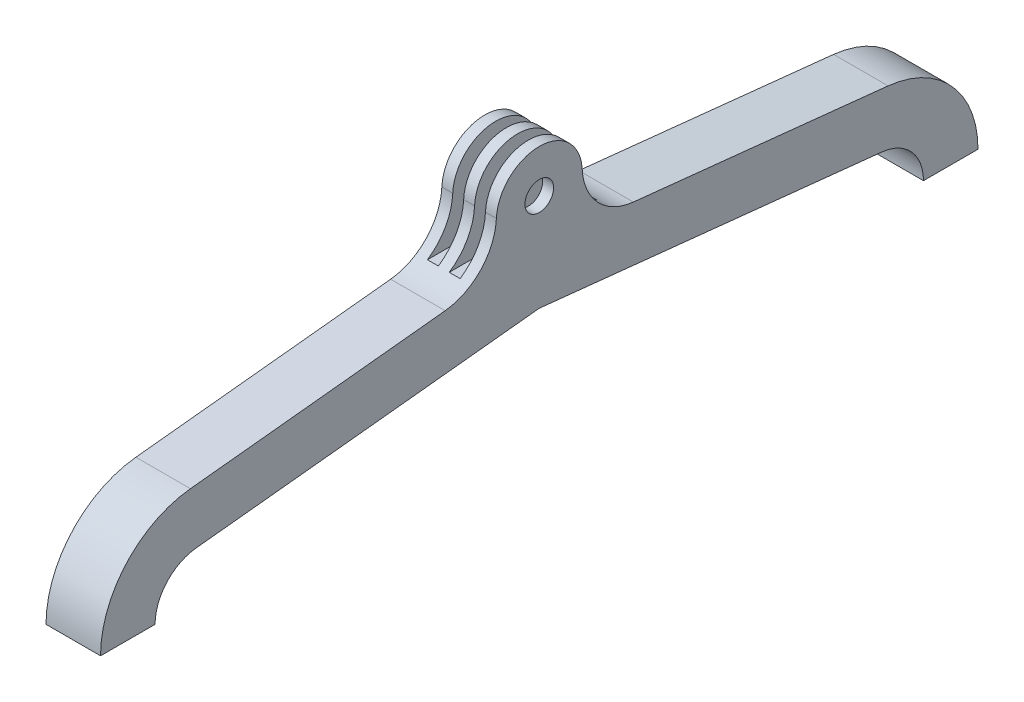
SolidWorks part; units mm, degrees
ref_plane "Front Plane" through (0, 0, 0) normal (0, 0, 1) x (1, 0, 0)
ref_plane "Top Plane" through (0, 0, 0) normal (0, 1, 0) x (1, 0, 0)
ref_plane "Right Plane" through (0, 0, 0) normal (1, 0, 0) x (0, 0, -1)
sketch "Sketch1" plane through (0, 0, 0) normal (1, 0, 0) x (0, 0, -1)
  line L0 (0, 0) -> (575, 0) construction
  line L1 (45.7424, 50.8) -> (287.5, 76.2)
  line L2 (575, 0) -> (575, -43.6699) construction
  line L3 (0, 0) -> (0, -49.9019) construction
  line L4 (287.5, 76.2) -> (529.2576, 50.8)
  arc A0 (0, 0) -> (45.7424, 50.8) centre (51.0796, 0) cw
  arc A1 (529.2576, 50.8) -> (575, 0) centre (523.9204, 0) cw
  dimension "D1" = 575
  dimension "D2" = 50.8
  dimension "D3" = 76.2
sketch "Sketch2" plane through (0, 0, 0) normal (0, 1, 0) x (1, 0, 0)
  line L0 (-19.05, -19.05) -> (19.05, -19.05)
  line L1 (-19.05, -19.05) -> (-19.05, 19.05)
  line L2 (19.05, -19.05) -> (19.05, 19.05)
  line L3 (-19.05, 19.05) -> (19.05, 19.05)
  line L4 (-19.05, -19.05) -> (19.05, 19.05) construction
  line L5 (19.05, -19.05) -> (-19.05, 19.05) construction
  point P1 (0, 0)
  dimension "D1" = 38.1
sweep "Sweep1" add profiles "Sketch2" path "Sketch1"
ref_point "Point1"
ref_point "Point2"
ref_axis "Axis1" through (0, 0, -575) along (0, -1, 0)
ref_axis "Axis2" through (0, 0, 0) along (0, -1, 0)
sketch "Sketch3" plane through (19.05, 0, 0) normal (1, 0, 0) x (0, 0, -1)
  line L6 (-19.05, 0) -> (19.05, 0)
  line L7 (47.7329, 31.8543) -> (287.5, 57.0451)
  line L8 (287.5, 57.0451) -> (527.2671, 31.8543)
  line L9 (555.95, 0) -> (594.05, 0)
  line L10 (531.2482, 69.7457) -> (287.5, 95.3549)
  line L11 (287.5, 95.3549) -> (43.7518, 69.7457)
  line L12 (-19.05, 0) -> (19.05, 0)
  line L13 (47.7329, 31.8543) -> (287.5, 57.0451)
  line L14 (287.5, 57.0451) -> (527.2671, 31.8543)
  line L15 (555.95, 0) -> (594.05, 0)
  line L16 (531.2482, 69.7457) -> (287.5, 95.3549)
  line L17 (287.5, 95.3549) -> (43.7518, 69.7457)
  circle A0 centre (287.5, 125) radius 10
  circle A1 centre (287.5, 125) radius 30
  arc A6 (43.7518, 69.7457) -> (-19.05, 0) centre (51.0796, 0) ccw
  arc A7 (47.7329, 31.8543) -> (19.05, 0) centre (51.0796, 0) ccw
  arc A8 (555.95, 0) -> (527.2671, 31.8543) centre (523.9204, 0) ccw
  arc A9 (594.05, 0) -> (531.2482, 69.7457) centre (523.9204, 0) ccw
  arc A10 (43.7518, 69.7457) -> (-19.05, 0) centre (51.0796, 0) ccw
  arc A11 (47.7329, 31.8543) -> (19.05, 0) centre (51.0796, 0) ccw
  arc A12 (555.95, 0) -> (527.2671, 31.8543) centre (523.9204, 0) ccw
  arc A13 (594.05, 0) -> (531.2482, 69.7457) centre (523.9204, 0) ccw
  line M20 (287.5, 95.3549) -> (43.7518, 69.7457)
  dimension "D2" = 20
  dimension "D3" = 60
  dimension "D1" = 125
  dimension "D4" = 0
extrude "Boss-Extrude1" add sketch "Sketch3" against normal up to surface (38.1 mm away) contours L16 A1 A0 M20 region at (19.05, 146.434, -267.7406) up to face at (-19.05, 39.0719, -287.5)
fillet "Fillet1" radius 40 2 edges at (0, 95.099, -289.9352) (0, 95.099, -285.0648)
ref_plane "Plane1" through (0, 155, 0) normal (0, 1, 0) x (1, 0, 0)
sketch "Sketch4" plane through (0, 155, 0) normal (0, 1, 0) x (1, 0, 0)
  line L0 (-19.05, 287.5) -> (-11.43, 287.5) construction
  line L1 (-11.43, 317.4681) -> (-3.81, 317.4681)
  line L2 (-11.43, 317.4681) -> (-11.43, 257.5319)
  line L3 (-11.43, 257.5319) -> (-3.81, 257.5319)
  line L4 (19.05, 257.5319) -> (19.05, 317.4681)
  line L5 (19.05, 317.4681) -> (-19.05, 317.4681)
  line L6 (-19.05, 317.4681) -> (-19.05, 257.5319)
  line L7 (-19.05, 257.5319) -> (19.05, 257.5319)
  line L8 (19.05, 257.5319) -> (19.05, 317.4681)
  line L9 (19.05, 317.4681) -> (-19.05, 317.4681)
  line L10 (-19.05, 317.4681) -> (-19.05, 257.5319)
  line L11 (-19.05, 257.5319) -> (19.05, 257.5319)
  line L12 (-3.81, 317.4681) -> (-3.81, 257.5319)
  line L13 (3.81, 317.4681) -> (11.43, 317.4681)
  line L14 (3.81, 317.4681) -> (3.81, 257.5319)
  line L15 (3.81, 257.5319) -> (11.43, 257.5319)
  line L16 (11.43, 317.4681) -> (11.43, 257.5319)
  line L17 (-11.43, 287.5) -> (-3.81, 287.5) construction
  line L18 (-3.81, 287.5) -> (3.81, 287.5) construction
  line L19 (3.81, 287.5) -> (11.43, 287.5) construction
  line L20 (11.43, 287.5) -> (19.05, 287.5) construction
  line L21 (-19.05, 353.246) -> (-19.05, 317.4681) construction
  line L22 (-19.05, 317.4681) -> (19.05, 317.4681) construction
  line L23 (19.05, 317.4681) -> (19.05, 353.246) construction
  line L24 (19.05, 353.246) -> (-19.05, 353.246) construction
  line L25 (-19.05, 257.5319) -> (-19.05, 221.754) construction
  line L26 (-19.05, 221.754) -> (19.05, 221.754) construction
  line L27 (19.05, 221.754) -> (19.05, 257.5319) construction
  line L28 (19.05, 257.5319) -> (-19.05, 257.5319) construction
  line L29 (-19.05, 353.246) -> (-19.05, 317.4681)
  line L30 (-19.05, 317.4681) -> (19.05, 317.4681)
  line L31 (19.05, 317.4681) -> (19.05, 353.246)
  line L32 (19.05, 353.246) -> (-19.05, 353.246)
  line L33 (-19.05, 257.5319) -> (-19.05, 221.754)
  line L34 (-19.05, 221.754) -> (19.05, 221.754)
  line L35 (19.05, 221.754) -> (19.05, 257.5319)
  line L36 (19.05, 257.5319) -> (-19.05, 257.5319)
  line L37 (-11.43, 317.4681) -> (-11.43, 353.246)
  line L38 (-3.81, 317.4681) -> (-3.81, 353.246)
  line L39 (3.81, 317.4681) -> (3.81, 353.246)
  line L40 (11.43, 317.4681) -> (11.43, 353.246)
  line L41 (-11.43, 257.5319) -> (-11.43, 221.754)
  line L42 (-3.81, 257.5319) -> (-3.81, 221.754)
  line L43 (3.81, 257.5319) -> (3.81, 221.754)
  line L44 (11.43, 257.5319) -> (11.43, 221.754)
  dimension "D1" = 0
extrude "Cut-Extrude1" cut sketch "Sketch4" against normal blind 60 contours L12 L1 L2 L3 | L1 L38 L32 L37 | L9 L40 L32 L39 | L16 L9 L14 L11 | L44 L11 L43 L34 | L42 L3 L41 L34 region at (-7.62, 155, -335.357) region at (-7.62, 155, -287.5) region at (-7.62, 155, -239.643) region at (7.62, 155, -335.357) region at (7.62, 155, -287.5) region at (7.62, 155, -239.643)
